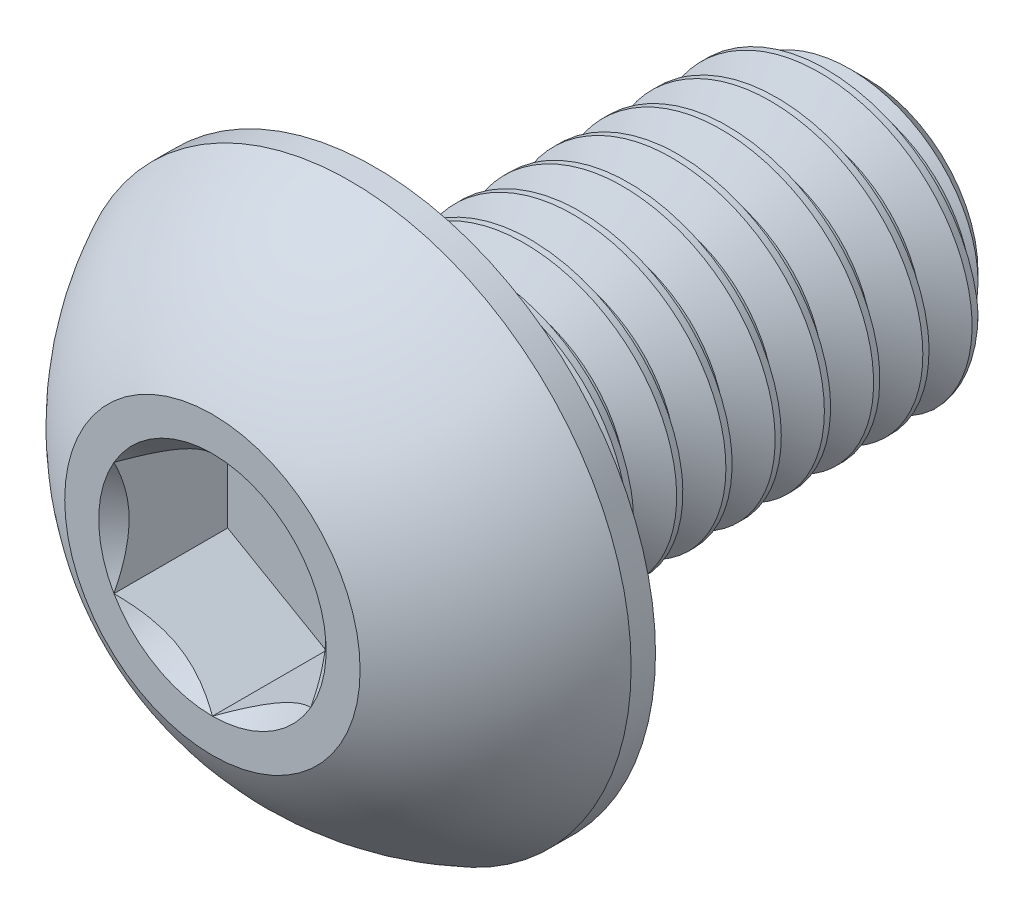
SolidWorks part; units mm, degrees
ref_plane "Front" through (0, 0, 0) normal (0, 0, 1) x (1, 0, 0)
ref_plane "Top" through (0, 0, 0) normal (0, 1, 0) x (1, 0, 0)
ref_plane "Right" through (0, 0, 0) normal (1, 0, 0) x (0, 0, -1)
sketch "Sketch1" plane through (0, 0, 0) normal (1, 0, 0) x (0, 0, -1)
  line L2 (1.65, 1.5) -> (6.65, 1.5)
  line L3 (6.65, 1.5) -> (6.65, 0)
  line L4 (6.65, 0) -> (1.65, 0)
  line L6 (1.4025, 2.85) -> (1.65, 2.85) construction
  line L7 (6.65, 1.5) -> (6.65, -1.5) construction
  line L8 (0, 0) -> (1.65, 0) construction
  line L9 (1.65, 2.85) -> (1.65, -2.85) construction
  line L11 (1.65, 1.5) -> (1.65, 0)
  line L13 (0, 1) -> (0, -1) construction
  line L14 (0, 1) -> (0, 1.5) construction
  arc A3 (0, 1.5) -> (1.4025, 2.85) centre (2.7948, 0) cw construction
  dimension "D1" = 0.2475
  dimension "Head Ht" = 1.65
  dimension "Head Dia" = 5.7
  dimension "Dia" = 3
  dimension "Lg" = 5
  dimension "Hex" = 2
revolve "Revolve1" add sketch "Sketch1" angle 360 mid plane about L4
sketch "Sketch3" plane through (0, 0, -6.65) normal (0, 0, -1) x (-1, 0, 0)
  circle A0 centre (0, 0) radius 1.5
curve "Helix/Spiral1" pitch 0.5 height 5.5 radius 1.5 centre (0, 0, -6.65) axis (0, 0, 1) start towards (0, 1, 0)
sketch "Sketch2" plane through (0, 0, 0) normal (1, 0, 0) x (0, 0, -1)
  line L0 (6.65, 1.5) -> (7.0875, 1.5)
  line L1 (7.0875, 1.5) -> (6.9, 1.1752)
  line L2 (6.9, 1.1752) -> (6.8375, 1.1752)
  line L3 (6.8375, 1.1752) -> (6.65, 1.5)
  line L4 (6.7438, 1.3376) -> (6.9938, 1.3376) construction
  dimension "D1" = 60
  dimension "D2" = 0.0625
  dimension "D3" = 0.25
chamfer "Chamfer1" distance 0.375 angle 45 1 edges at (0, 1.5, -6.65)
sweep "Cut-Sweep1" cut profiles "Sketch2" path "Helix/Spiral1" align with end faces yes
sketch "Sketch7" plane through (0, 0, 0) normal (1, 0, 0) x (0, 0, -1)
  line L6 (1.4025, 2.85) -> (1.65, 2.85) construction
  line L8 (0, 0) -> (1.65, 0) construction
  line L11 (1.65, 2.85) -> (1.65, -2.85) construction
  line L12 (1.4025, 2.85) -> (1.65, 2.85)
  line L13 (0, 0) -> (1.65, 0)
  line L14 (0, 1) -> (0, -1) construction
  line L15 (1.65, 2.85) -> (1.65, 0)
  line L16 (0, 1.5) -> (0, 0)
  arc A2 (1.4025, 2.85) -> (0, 1.5) centre (2.7948, 0) ccw construction
  arc A3 (1.4025, 2.85) -> (0, 1.5) centre (2.7948, 0) ccw
revolve "Revolve2" add sketch "Sketch7" angle 360 mid plane about L13
sketch "Sketch5" plane through (0, 0, 0) normal (0, 0, 1) x (1, 0, 0)
  line L1 (1, -0.5774) -> (1, 0.5774)
  line L2 (1, 0.5774) -> (0, 1.1547)
  line L3 (0, 1.1547) -> (-1, 0.5774)
  line L4 (-1, 0.5774) -> (-1, -0.5774)
  line L5 (-1, -0.5774) -> (0, -1.1547)
  line L6 (0, -1.1547) -> (1, -0.5774)
  circle A0 centre (0, 0) radius 1 construction
extrude "Cut-Extrude2" cut sketch "Sketch5" against normal blind 1.155
sketch "Sketch6" plane through (0, 0, 0) normal (0, 0, 1) x (1, 0, 0)
  circle A0 centre (0, 0) radius 1.1547
extrude "Cut-Extrude3" cut sketch "Sketch6" against normal blind 1.155 draft 45
sketch "Sketch9" [suppressed] plane through (0, 0, -4.2164) normal (0, 0, 1) x (1, 0, 0)
  circle A2 centre (0, 0) radius 3.9687
extrude "Boss-Extrude2" [suppressed] add sketch "Sketch9" against normal offset from surface (9.525 mm away) 28.575 up to face at (0, 1.125, -6.65)
sketch "Sketch10" plane through (0, 0, 0) normal (1, 0, 0) x (0, 0, -1)
  line L0 (6.65, 1.5) -> (6.65, -1.5) construction
  point P0 (5.9, -1.5)
  dimension "D1" = 0.75
equation "\"D3@Helix/Spiral1\" = \"Lg@Sketch1\" + \"D4@Helix/Spiral1\""
equation "\"D2@Sketch2\" = \"D4@Helix/Spiral1\" * .125"
equation "\"D3@Sketch2\" = \"D4@Helix/Spiral1\" * .5"
equation "\"D1@Chamfer1\" = \"D4@Helix/Spiral1\" * .75"
equation "\"D1@Cut-Extrude2\" = \"Head Ht@Sketch1\" * .7"
equation "\"D1@Sketch1\" = \"Head Ht@Sketch1\" * .15"
equation "\"D1@Sketch10\" = \"D4@Helix/Spiral1\" * 1.5"
equation "\"D1@Cut-Extrude3\" = \"D1@Cut-Extrude2\""
